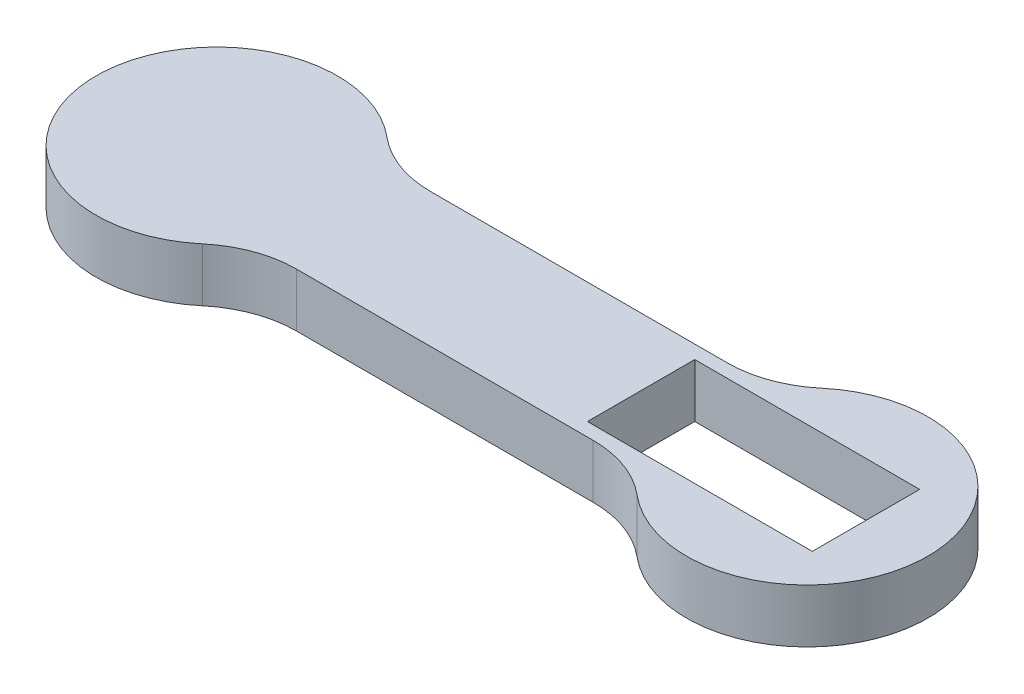
SolidWorks part; units mm, degrees
material "ABS"
ref_plane "Front Plane" through (0, 0, 0) normal (0, 0, 1) x (1, 0, 0)
ref_plane "Top Plane" through (0, 0, 0) normal (0, 1, 0) x (1, 0, 0)
ref_plane "Right Plane" through (0, 0, 0) normal (1, 0, 0) x (0, 0, -1)
other "Center of Mass"
sketch "Sketch2" plane through (0, 0, 0) normal (0, 1, 0) x (1, 0, 0)
  line L0 (0, 0) -> (136.4639, 0) construction
  line L1 (27.3861, 12.5) -> (82.6139, 12.5)
  line L2 (182.7618, 2.3639) -> (182.7525, -2.6361) construction
  line L3 (27.3861, -12.5) -> (82.6139, -12.5)
  line L5 (137.9207, 0) -> (181.8456, 0) construction
  arc A0 (14.4985, 17.2059) -> (14.4985, -17.2059) centre (0, 0) ccw
  arc A1 (95.5015, -17.2059) -> (95.5015, 17.2059) centre (110, 0) ccw
  arc A2 (95.5015, -17.2059) -> (82.6139, -12.5) centre (82.6139, -32.5) ccw
  arc A3 (95.5015, 17.2059) -> (82.6139, 12.5) centre (82.6139, 32.5) cw
  arc A4 (27.3861, -12.5) -> (14.4985, -17.2059) centre (27.3861, -32.5) ccw
  arc A5 (27.3861, 12.5) -> (14.4985, 17.2059) centre (27.3861, 32.5) cw
  point P16 (18.7083, -12.5)
  point P19 (18.7083, 12.5)
  dimension "D1" = 45
  dimension "D4" = 45
  dimension "D5" = 20
  dimension "D2" = 25
  dimension "D3" = 110
extrude "Boss-Extrude1" add sketch "Sketch2" along normal blind 10
sketch "Sketch3" plane through (0, 10, 0) normal (0, 1, 0) x (1, 0, 0)
  line L0 (0, 0) -> (125.1104, 0) construction
  line L1 (125.1104, 0) -> (159.77, 0) construction
  line L3 (73, -10) -> (127, -10)
  line L4 (73, -10) -> (73, 10)
  line L5 (73, 10) -> (127, 10)
  line L6 (127, -10) -> (127, 10)
  line L7 (73, -10) -> (127, 10) construction
  line L8 (73, 10) -> (127, -10) construction
  line L9 (79.05, -10.5) -> (120.95, -10.5)
  line L10 (79.05, -10.5) -> (79.05, 10.5)
  line L11 (79.05, 10.5) -> (120.95, 10.5)
  line L12 (120.95, -10.5) -> (120.95, 10.5)
  line L13 (79.05, -10.5) -> (120.95, 10.5) construction
  line L14 (79.05, 10.5) -> (120.95, -10.5) construction
  arc A0 (95.5015, -17.2059) -> (95.5015, 17.2059) centre (110, 0) ccw construction
  point P4 (100, 0)
  point P12 (100, 0)
  dimension "D2" = 17
  dimension "D1" = 20
  dimension "D3" = 54
  dimension "D4" = 41.9
  dimension "D5" = 21
extrude "Cut-Extrude1" cut sketch "Sketch3" against normal through all contours L3 L12 L5 L10 region at (100, 10, 0)
